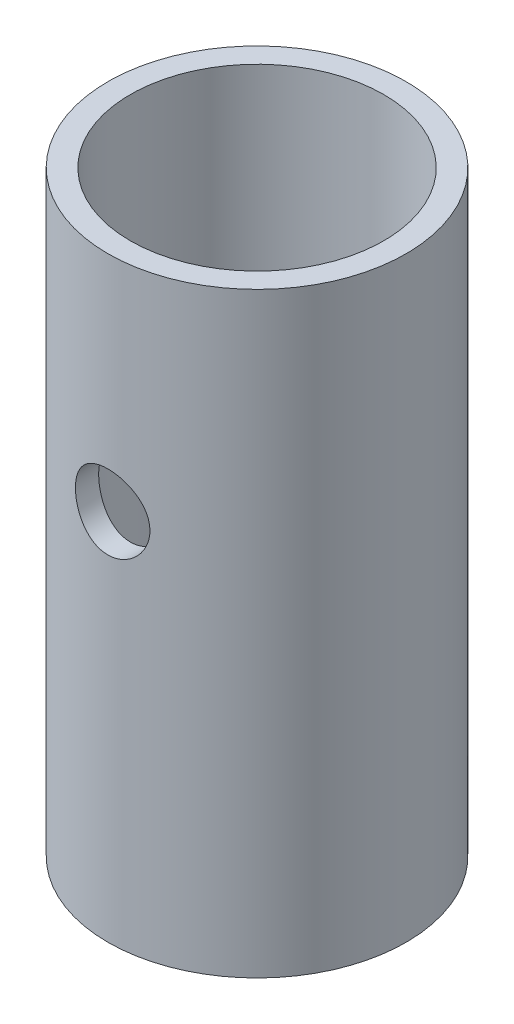
SolidWorks part; units mm, degrees
ref_plane "Front Plane" through (0, 0, 0) normal (0, 0, 1) x (1, 0, 0)
ref_plane "Top Plane" through (0, 0, 0) normal (0, 1, 0) x (1, 0, 0)
ref_plane "Right Plane" through (0, 0, 0) normal (1, 0, 0) x (0, 0, -1)
sketch "Sketch1" plane through (0, 0, 0) normal (0, 1, 0) x (1, 0, 0)
  circle A0 centre (0, 0) radius 5
  dimension "D1" = 10
extrude "Boss-Extrude1" add sketch "Sketch1" along normal blind 20 contours A0
sketch "Sketch2" plane through (0, 20, 0) normal (0, 1, 0) x (1, 0, 0)
  circle A0 centre (0, 0) radius 4.25
  dimension "D1" = 8.5
extrude "Cut-Extrude1" cut sketch "Sketch2" against normal blind 17.5 contours A0
sketch "Sketch3" plane through (0, 0, 0) normal (0, -1, 0) x (1, 0, 0)
  circle A0 centre (0, 0) radius 1.25
  dimension "D1" = 2.5
extrude "Cut-Extrude2" cut sketch "Sketch3" against normal blind 2.5
sketch "Sketch4" plane through (0, 0, 0) normal (0, 0, 1) x (1, 0, 0)
  line L0 (4.25, 20) -> (-4.25, 20) construction
  circle A0 centre (0, 12.5) radius 1.25
  dimension "D2" = 2.5
  dimension "D1" = 7.5
extrude "Cut-Extrude3" cut sketch "Sketch4" against normal blind 10 and the other way blind 10
